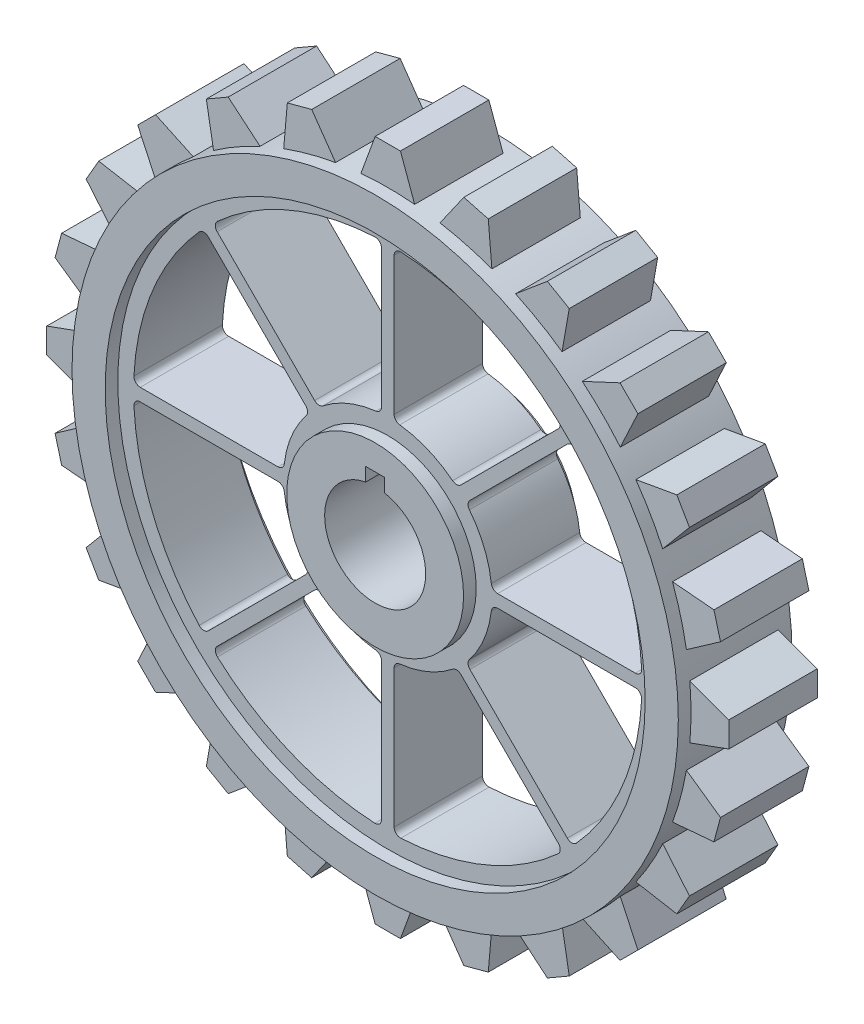
SolidWorks part; units mm, degrees
ref_plane "Front Plane" through (0, 0, 0) normal (0, 0, 1) x (1, 0, 0)
ref_plane "Top Plane" through (0, 0, 0) normal (0, 1, 0) x (1, 0, 0)
ref_plane "Right Plane" through (0, 0, 0) normal (1, 0, 0) x (0, 0, -1)
sketch "Sketch1" plane through (0, 0, 0) normal (0, 0, 1) x (1, 0, 0)
  line L0 (-1903.0403, 0) -> (93248.9725, 0) construction
  line L1 (0, -1903.0403) -> (0, 93248.9725) construction
  line L2 (-2, 54) -> (2, 54)
  line L3 (-4.2525, 47.8113) -> (-2, 54)
  line L4 (4.2525, 47.8113) -> (2, 54)
  circle A0 centre (0, 0) radius 48
  arc A1 (-4.2525, 47.8113) -> (4.2525, 47.8113) centre (0, 0) cw
  point P7 (0, 48)
  point P11 (0, 54)
  dimension "D1" = 96
  dimension "D2" = 4
  dimension "D3" = 6
  dimension "D4" = 40
extrude "Boss-Extrude5" add sketch "Sketch1" against normal blind 14 from offset 2 contours L4 L2 L3 A1 offset against normal yes
extrude "Boss-Extrude6" add sketch "Sketch1<8>" against normal blind 18 contours A0 region at (0, 0, 0)
sketch "Sketch1<8>" plane through (0, 0, 0) normal (0, 0, 1) x (1, 0, 0) same geometry as "Sketch1"
pattern_circular "CirPattern2" count 24 over 360 about axis through (0, 0, 0) along (0, 0, 1) of "Boss-Extrude5"
sketch "Sketch2" plane through (0, 0, 0) normal (0, 0, 1) x (1, 0, 0)
  line L0 (0, -1000) -> (0, 49000) construction
  line L1 (1, 39.199) -> (1, 17.3853)
  line L2 (-1, 39.199) -> (-1, 17.3853)
  line L3 (27.0108, 28.425) -> (11.5862, 13.0004)
  line L4 (28.425, 27.0108) -> (13.0004, 11.5862)
  line L5 (39.199, 1) -> (17.3853, 1)
  line L6 (39.199, -1) -> (17.3853, -1)
  line L7 (28.425, -27.0108) -> (13.0004, -11.5862)
  line L8 (27.0108, -28.425) -> (11.5862, -13.0004)
  line L9 (1, -39.199) -> (1, -17.3853)
  line L10 (-1, -39.199) -> (-1, -17.3853)
  line L11 (-27.0108, -28.425) -> (-11.5862, -13.0004)
  line L12 (-28.425, -27.0108) -> (-13.0004, -11.5862)
  line L13 (-39.199, -1) -> (-17.3853, -1)
  line L14 (-39.199, 1) -> (-17.3853, 1)
  line L15 (-28.425, 27.0108) -> (-13.0004, 11.5862)
  line L16 (-27.0108, 28.425) -> (-11.5862, 13.0004)
  line L17 (-11.5862, 13.0004) -> (-27.0108, 28.425)
  line L18 (-1, 39.199) -> (-1, 17.3853)
  circle A0 centre (0, 0) radius 42.75
  arc A1 (-2.051, 40.1977) -> (-26.9738, 29.8743) centre (0, 0) ccw
  circle A2 centre (0, 0) radius 14
  arc A3 (-1.8857, 16.3919) -> (-10.2574, 12.9242) centre (0, 0) ccw
  arc A4 (2.051, 40.1977) -> (1, 39.199) centre (2, 39.199) ccw
  arc A5 (1.8857, 16.3919) -> (1, 17.3853) centre (2, 17.3853) cw
  arc A6 (-1.8857, 16.3919) -> (-1, 17.3853) centre (-2, 17.3853) ccw
  arc A7 (-2.051, 40.1977) -> (-1, 39.199) centre (-2, 39.199) cw
  arc A8 (29.8743, 26.9738) -> (28.425, 27.0108) centre (29.1321, 26.3037) ccw
  circle A9 centre (0, 0) radius 40.25 construction
  circle A10 centre (0, 0) radius 16.5 construction
  arc A11 (26.9738, 29.8743) -> (27.0108, 28.425) centre (26.3037, 29.1321) cw
  arc A12 (12.9242, 10.2574) -> (13.0004, 11.5862) centre (13.7075, 10.8791) cw
  arc A13 (10.2574, 12.9242) -> (11.5862, 13.0004) centre (10.8791, 13.7075) ccw
  arc A14 (40.1977, -2.051) -> (39.199, -1) centre (39.199, -2) ccw
  arc A15 (40.1977, 2.051) -> (39.199, 1) centre (39.199, 2) cw
  arc A16 (16.3919, -1.8857) -> (17.3853, -1) centre (17.3853, -2) cw
  arc A17 (16.3919, 1.8857) -> (17.3853, 1) centre (17.3853, 2) ccw
  arc A18 (26.9738, -29.8743) -> (27.0108, -28.425) centre (26.3037, -29.1321) ccw
  arc A19 (29.8743, -26.9738) -> (28.425, -27.0108) centre (29.1321, -26.3037) cw
  arc A20 (10.2574, -12.9242) -> (11.5862, -13.0004) centre (10.8791, -13.7075) cw
  arc A21 (12.9242, -10.2574) -> (13.0004, -11.5862) centre (13.7075, -10.8791) ccw
  arc A22 (-2.051, -40.1977) -> (-1, -39.199) centre (-2, -39.199) ccw
  arc A23 (2.051, -40.1977) -> (1, -39.199) centre (2, -39.199) cw
  arc A24 (-1.8857, -16.3919) -> (-1, -17.3853) centre (-2, -17.3853) cw
  arc A25 (1.8857, -16.3919) -> (1, -17.3853) centre (2, -17.3853) ccw
  arc A26 (-29.8743, -26.9738) -> (-28.425, -27.0108) centre (-29.1321, -26.3037) ccw
  arc A27 (-26.9738, -29.8743) -> (-27.0108, -28.425) centre (-26.3037, -29.1321) cw
  arc A28 (-12.9242, -10.2574) -> (-13.0004, -11.5862) centre (-13.7075, -10.8791) cw
  arc A29 (-10.2574, -12.9242) -> (-11.5862, -13.0004) centre (-10.8791, -13.7075) ccw
  arc A30 (-40.1977, 2.051) -> (-39.199, 1) centre (-39.199, 2) ccw
  arc A31 (-40.1977, -2.051) -> (-39.199, -1) centre (-39.199, -2) cw
  arc A32 (-16.3919, 1.8857) -> (-17.3853, 1) centre (-17.3853, 2) cw
  arc A33 (-16.3919, -1.8857) -> (-17.3853, -1) centre (-17.3853, -2) ccw
  arc A34 (-26.9738, 29.8743) -> (-27.0108, 28.425) centre (-26.3037, 29.1321) ccw
  arc A35 (-29.8743, 26.9738) -> (-28.425, 27.0108) centre (-29.1321, 26.3037) cw
  arc A36 (-10.2574, 12.9242) -> (-11.5862, 13.0004) centre (-10.8791, 13.7075) cw
  arc A37 (-12.9242, 10.2574) -> (-13.0004, 11.5862) centre (-13.7075, 10.8791) ccw
  arc A38 (-29.8743, 26.9738) -> (-40.1977, 2.051) centre (0, 0) ccw
  arc A39 (40.1977, 2.051) -> (29.8743, 26.9738) centre (0, 0) ccw
  arc A40 (16.3919, 1.8857) -> (12.9242, 10.2574) centre (0, 0) ccw
  arc A41 (10.2574, 12.9242) -> (1.8857, 16.3919) centre (0, 0) ccw
  arc A42 (-12.9242, 10.2574) -> (-16.3919, 1.8857) centre (0, 0) ccw
  arc A43 (-16.3919, -1.8857) -> (-12.9242, -10.2574) centre (0, 0) ccw
  arc A44 (-10.2574, -12.9242) -> (-1.8857, -16.3919) centre (0, 0) ccw
  arc A45 (12.9242, -10.2574) -> (16.3919, -1.8857) centre (0, 0) ccw
  arc A46 (1.8857, -16.3919) -> (10.2574, -12.9242) centre (0, 0) ccw
  arc A47 (26.9738, 29.8743) -> (2.051, 40.1977) centre (0, 0) ccw
  arc A48 (29.8743, -26.9738) -> (40.1977, -2.051) centre (0, 0) ccw
  arc A49 (2.051, -40.1977) -> (26.9738, -29.8743) centre (0, 0) ccw
  arc A50 (-26.9738, -29.8743) -> (-2.051, -40.1977) centre (0, 0) ccw
  arc A51 (-40.1977, -2.051) -> (-29.8743, -26.9738) centre (0, 0) ccw
  arc A52 (-2.051, 40.1977) -> (-26.9738, 29.8743) centre (0, 0) ccw
  arc A53 (-27.0108, 28.425) -> (-26.9738, 29.8743) centre (-26.3037, 29.1321) cw
  arc A54 (-10.2574, 12.9242) -> (-11.5862, 13.0004) centre (-10.8791, 13.7075) cw
  arc A55 (-10.2574, 12.9242) -> (-1.8857, 16.3919) centre (0, 0) cw
  arc A56 (-1.8857, 16.3919) -> (-1.0575, 17.0511) centre (-2, 17.3853) ccw
  point P4 (16.5, 0)
  point P22 (40.25, 0)
  point P111 (0, 0)
  dimension "D1" = 85.5
  dimension "D3" = 28
  dimension "D5" = 1
  dimension "D7" = 1
  dimension "D6" = 1
  dimension "D2" = 2.5
  dimension "D4" = 2.5
  dimension "D8" = 8
extrude "Cut-Extrude3" cut sketch "Sketch2" against normal blind 2 contours A0 A51 A31 L13 A33 A43 A28 L12 A26 A50 A27 L11 A29 A44 A24 L10 A22 A49 A23 L9 A25 A46 A20 L8 A18 A48 A19 L7 A21 A45 A16 L6 A14 A47 A11 L3 A13 A41 A5 L1 A4 A2 A3 A36 region at (-41.5408, 0, 0)
ref_plane "Plane1" through (0, 0, -9) normal (0, 0, 1) x (1, 0, 0)
mirror "Mirror2" about plane through (0, 0, -9) normal (0, 0, 1) of "Cut-Extrude3"
ref_plane "Plane2" through (0, 0, 0) normal (0, 0, 1) x (1, 0, 0)
sketch "Sketch3" plane through (0, 0, 0) normal (0, 0, 1) x (1, 0, 0)
  line L0 (-27.0108, 28.425) -> (-11.5862, 13.0004)
  line L1 (-1, 17.3853) -> (-1, 39.199)
  arc A0 (-26.9738, 29.8743) -> (-2.051, 40.1977) centre (0, 0) cw
  arc A1 (-2.051, 40.1977) -> (-1, 39.199) centre (-2, 39.199) cw
  arc A2 (-1, 39.199) -> (-2.051, 40.1977) centre (-2, 39.199) ccw construction
  arc A3 (-27.0108, 28.425) -> (-26.9738, 29.8743) centre (-26.3037, 29.1321) cw
  arc A4 (-26.9738, 29.8743) -> (-27.0108, 28.425) centre (-26.3037, 29.1321) ccw construction
  arc A5 (-11.5862, 13.0004) -> (-10.2574, 12.9242) centre (-10.8791, 13.7075) ccw
  arc A6 (-11.5862, 13.0004) -> (-10.2574, 12.9242) centre (-10.8791, 13.7075) ccw construction
  arc A7 (-1.8857, 16.3919) -> (-10.2574, 12.9242) centre (0, 0) ccw construction
  arc A8 (-10.2574, 12.9242) -> (-1.8857, 16.3919) centre (0, 0) cw
  arc A9 (-1.8857, 16.3919) -> (-1, 17.3853) centre (-2, 17.3853) ccw construction
  arc A10 (-1, 17.3853) -> (-1.8857, 16.3919) centre (-2, 17.3853) cw
extrude "Cut-Extrude5" cut sketch "Sketch3" against normal up to next
pattern_circular "CirPattern3" count 8 over 360 about axis through (0, 0, -2) along (0, 0, 1) of "Cut-Extrude5"
sketch "Sketch4" plane through (0, 0, 0) normal (0, 0, 1) x (1, 0, 0)
  line L0 (0, -1000) -> (0, 49000) construction
  line L1 (-1.5, 10) -> (1.5, 10)
  line L2 (-1.5, 10) -> (-1.5, 7.8581)
  line L3 (1.5, 10) -> (1.5, 7.8581)
  arc A0 (-1.5, 7.8581) -> (1.5, 7.8581) centre (0, 0) ccw
  point P8 (0, 10)
  dimension "D1" = 16
  dimension "D2" = 3
  dimension "D3" = 10
extrude "Cut-Extrude7" cut sketch "Sketch4" against normal up to next
